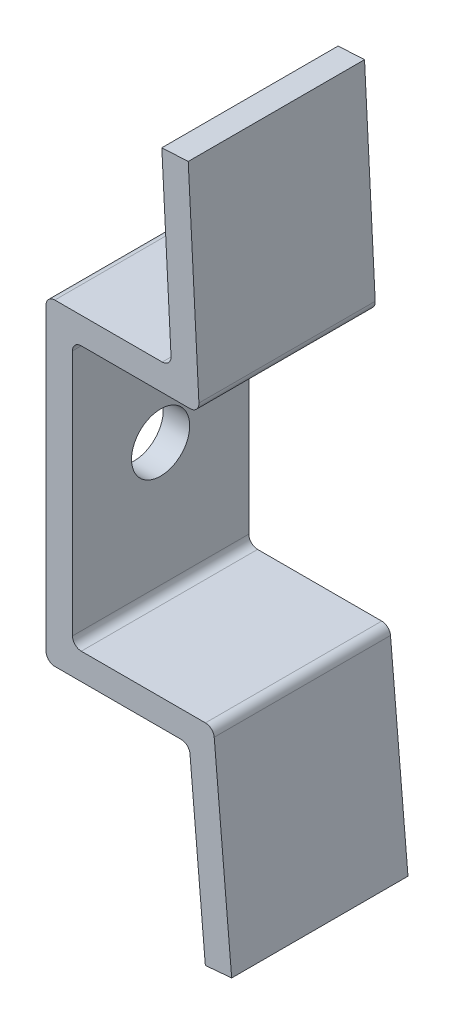
SolidWorks part; units mm, degrees
ref_plane "Спереди" through (0, 0, 0) normal (0, 0, 1) x (1, 0, 0)
ref_plane "Сверху" through (0, 0, 0) normal (0, 1, 0) x (1, 0, 0)
ref_plane "Справа" through (0, 0, 0) normal (1, 0, 0) x (0, 0, -1)
sketch "Эскиз1" plane through (0, 0, 0) normal (0, 0, 1) x (1, 0, 0)
  line L0 (0, 17) -> (0, -17)
  line L1 (1, -18) -> (15.3347, -18)
  line L2 (16.3309, -18.9128) -> (18.074, -38.8367)
  line L3 (18.074, -38.8367) -> (21.0626, -38.5753)
  line L4 (21.0626, -38.5753) -> (19.0799, -15.9128)
  line L5 (18.0837, -15) -> (4, -15)
  line L6 (3, -14) -> (3, 14)
  line L7 (4, 15) -> (16.3462, 15)
  line L8 (17.3448, 16.0523) -> (16.1327, 39.1819)
  line L9 (16.1327, 39.1819) -> (13.1368, 39.0249)
  line L12 (13.1368, 39.0249) -> (14.1835, 19.0523)
  line L13 (13.1849, 18) -> (1, 18)
  arc A0 (14.1835, 19.0523) -> (13.1849, 18) centre (13.1849, 19) cw
  arc A1 (16.3462, 15) -> (17.3448, 16.0523) centre (16.3462, 16) ccw
  arc A2 (19.0799, -15.9128) -> (18.0837, -15) centre (18.0837, -16) ccw
  arc A3 (15.3347, -18) -> (16.3309, -18.9128) centre (15.3347, -19) cw
  arc A4 (0, -17) -> (1, -18) centre (1, -17) ccw
  arc A5 (4, -15) -> (3, -14) centre (4, -14) cw
  arc A6 (3, 14) -> (4, 15) centre (4, 14) cw
  arc A7 (0, 17) -> (1, 18) centre (1, 17) cw
  point P17 (17.4, 15)
  point P20 (19, -15)
  point P29 (3, 15)
  dimension "D12" = 1
  dimension "D1" = 3
  dimension "D2" = 3
  dimension "D3" = 3
  dimension "D4" = 30
  dimension "D5" = 15
  dimension "D6" = 3
  dimension "D7" = 3
  dimension "D8" = 87
  dimension "D9" = 16
  dimension "D10" = 14.4
  dimension "D11" = 95
  dimension "D13" = 20
  dimension "D14" = 20
extrude "Бобышка-Вытянуть1" add sketch "Эскиз1" along normal blind 10 and the other way blind 10
hole_wizard "Отверстие с зазором M61" positions "Трехмерный эскиз1" profile "Эскиз2" hole size "M6" standard "ISO" end condition through all
sketch3d "Трехмерный эскиз1"
  point P11 (0, 0, 0)
sketch "Эскиз2" plane through (0, 0, 0) normal (0, 1, 0) x (0, 0, 1)
  line L0 (0, 0) -> (0, 21.0626)
  line L1 (0, 21.0626) -> (3.3, 21.0626)
  line L2 (3.3, 21.0626) -> (3.3, 0)
  line L5 (3.3, 0) -> (0, 0)
  line L11 (0, -6.35) -> (0, 107.95) construction
  dimension "Диаметр сквозного отверстия" = 6.6
  dimension "Глубина сквозного отверстия" = 21.0626
